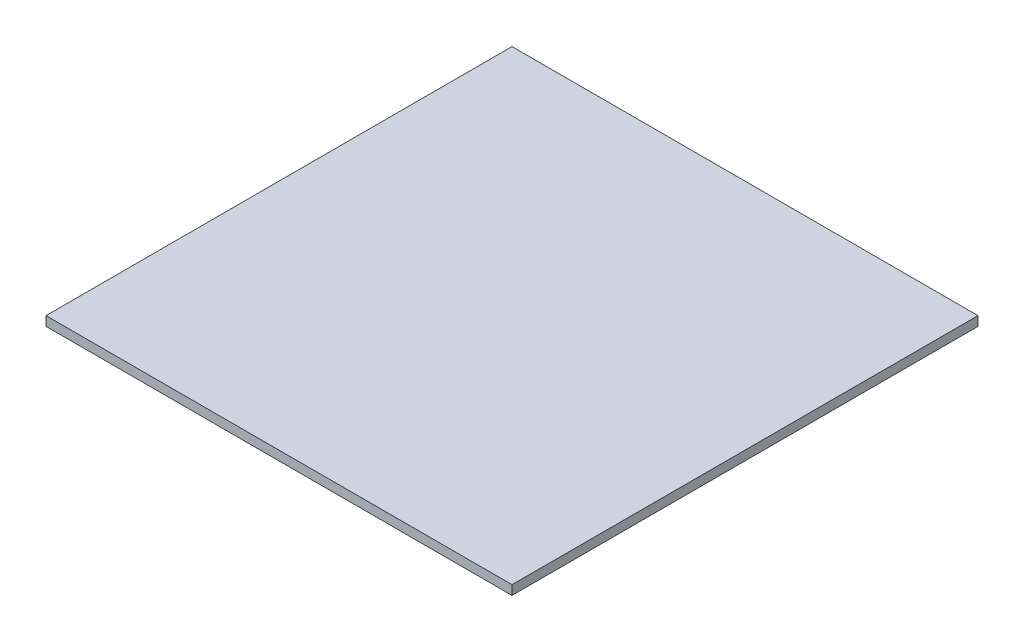
SolidWorks part; units mm, degrees
material "6061-T4 (SS)"
ref_plane "Front Plane" through (0, 0, 0) normal (0, 0, 1) x (1, 0, 0)
ref_plane "Top Plane" through (0, 0, 0) normal (0, 1, 0) x (1, 0, 0)
ref_plane "Right Plane" through (0, 0, 0) normal (1, 0, 0) x (0, 0, -1)
sketch "Sketch1" plane through (0, 0, 0) normal (0, 1, 0) x (1, 0, 0)
  line L1 (0, 0) -> (100, 0)
  line L2 (0, 0) -> (0, 100)
  line L3 (0, 100) -> (100, 100)
  line L4 (100, 0) -> (100, 100)
  dimension "D1" = 100
  dimension "D2" = 100
extrude "Boss-Extrude1" add sketch "Sketch1" along normal blind 2
